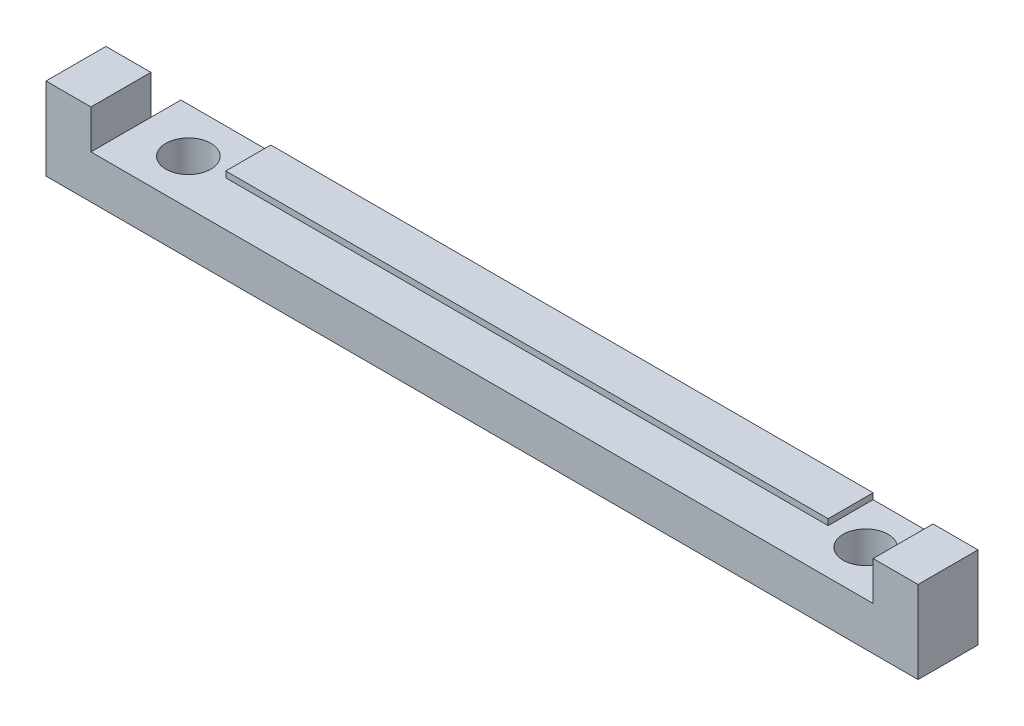
SolidWorks part; units mm, degrees
ref_plane "Front Plane" through (0, 0, 0) normal (0, 0, 1) x (1, 0, 0)
ref_plane "Top Plane" through (0, 0, 0) normal (0, 1, 0) x (1, 0, 0)
ref_plane "Right Plane" through (0, 0, 0) normal (1, 0, 0) x (0, 0, -1)
sketch "Sketch1" plane through (0, 0, 0) normal (0, 0, 1) x (1, 0, 0)
  line L0 (0, 5.5) -> (0, 0)
  line L1 (0, 0) -> (58.2, 0)
  line L2 (58.2, 0) -> (58.2, 5.5)
  line L3 (58.2, 5.5) -> (55.2, 5.5)
  line L4 (55.2, 5.5) -> (55.2, 2.9)
  line L5 (55.2, 2.9) -> (3, 2.9)
  line L6 (3, 2.9) -> (3, 5.5)
  line L7 (3, 5.5) -> (0, 5.5)
  dimension "D1" = 5.5
  dimension "D2" = 3
  dimension "D3" = 58.2
  dimension "D4" = 2.9
extrude "Boss-Extrude1" add sketch "Sketch1" along normal blind 6
sketch "Sketch3" plane through (0, 5.5, 0) normal (0, 1, 0) x (1, 0, 0)
  line L1 (0, 0) -> (3, 0)
  line L2 (0, 0) -> (0, -2)
  line L3 (0, -2) -> (3, -2)
  line L4 (3, 0) -> (3, -2)
  line L5 (58.2, 0) -> (55.2, 0)
  line L6 (58.2, 0) -> (58.2, -2)
  line L7 (58.2, -2) -> (55.2, -2)
  line L8 (55.2, 0) -> (55.2, -2)
  dimension "D1" = 3
  dimension "D2" = 2
extrude "Cut-Extrude2" cut sketch "Sketch3" against normal up to next
sketch "Sketch4" plane through (0, 5.5, 0) normal (0, 1, 0) x (1, 0, 0)
  line L1 (3, -6) -> (0, -6) construction
  line L3 (0, -6) -> (0, -2) construction
  line L4 (58.2, -6) -> (58.2, -2) construction
  circle A0 centre (6.5, -3) radius 1.5
  circle A1 centre (51.7, -3) radius 1.5
  dimension "D1" = 3
  dimension "D2" = 6.5
  dimension "D3" = 3
  dimension "D4" = 6.5
extrude "Cut-Extrude3" cut sketch "Sketch4" against normal up to next
sketch "Sketch5" plane through (0, 2.9, 0) normal (0, 1, 0) x (1, 0, 0)
  line L0 (9, -3) -> (49.2, -3)
  line L2 (49.2, -3) -> (49.2, 0)
  line L3 (49.2, 0) -> (9, 0)
  line L4 (9, 0) -> (9, -3)
  line L5 (3, -6) -> (3, -2) construction
  line L6 (55.2, -6) -> (55.2, -2) construction
  line L8 (55.2, 0) -> (3, 0) construction
  dimension "D1" = 6
  dimension "D2" = 6
  dimension "D3" = 3
extrude "Boss-Extrude2" add sketch "Sketch5" along normal blind 0.4
